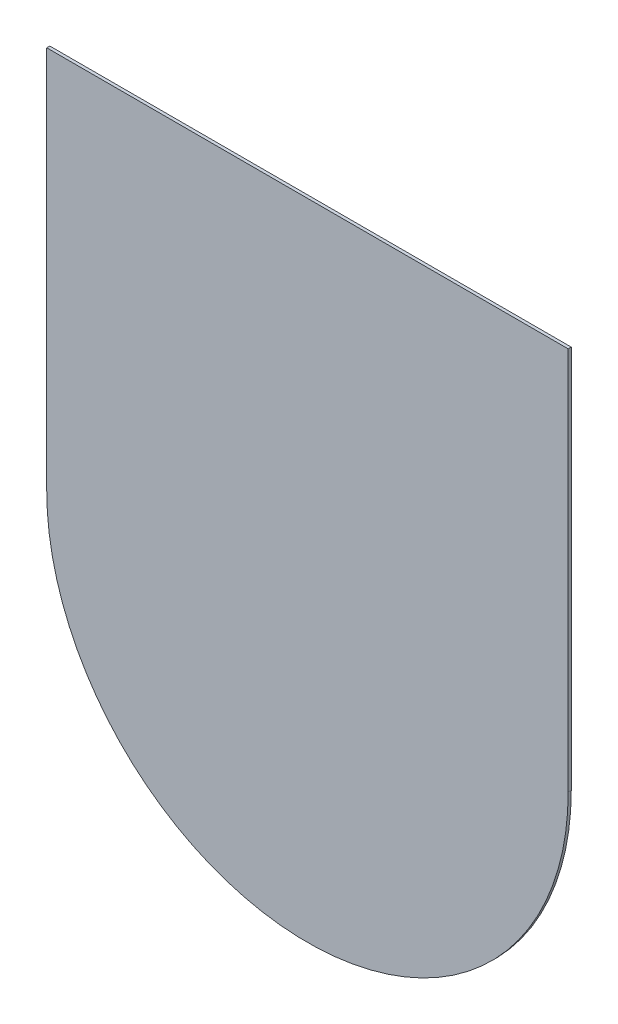
SolidWorks part; units mm, degrees
ref_plane "Front Plane" through (0, 0, 0) normal (0, 0, 1) x (1, 0, 0)
ref_plane "Top Plane" through (0, 0, 0) normal (0, 1, 0) x (1, 0, 0)
ref_plane "Right Plane" through (0, 0, 0) normal (1, 0, 0) x (0, 0, -1)
sketch "Sketch1" plane through (0, 0, 0) normal (0, 0, 1) x (-1, 0, 0)
  line L2 (-169.8665, -250) -> (-169.8665, 0)
  line L4 (169.8665, -250) -> (169.8665, 0)
  line L6 (0.1, 0) -> (0.1, -250) construction
  line L7 (-169.8665, -250) -> (169.8665, -250)
  line L8 (-208.1086, -301.1946) -> (249.5564, -301.1946) construction
  arc A0 (169.8665, 0) -> (-169.8665, 0) centre (0, 0) ccw
  point P9 (0.1, -280.3559)
base flange "Base-Flange1" sketch "Sketch1" thickness 2 reverse thickness direction no parameters "D1"=0.7366
sketch "Bend-Lines1" [suppressed] plane through (0, 0, 0) normal (0, 1, 0) x (1, 0, 0)
sketch "Bounding-Box1" [suppressed] plane through (0, 0, 0) normal (0, 1, 0) x (1, 0, 0)
sheet metal parameters "Sheet-Metal1" thickness 2 parameters "D1"=0.7366
flat pattern "Flat-Pattern1" [suppressed]
sketch "Bend-Lines2" plane through (0, 0, 0) normal (0, 1, 0) x (1, 0, 0)
sketch3d "Bounding-Box2" [suppressed]
  line L0 (169.8665, -169.8665, 0) -> (169.8665, 250, 0) construction
  line L1 (-169.8665, -169.8665, 0) -> (-169.8665, 250, 0) construction
  line L2 (169.8665, -169.8665, 0) -> (-169.8665, -169.8665, 0) construction
  line L3 (169.8665, 250, 0) -> (-169.8665, 250, 0) construction
